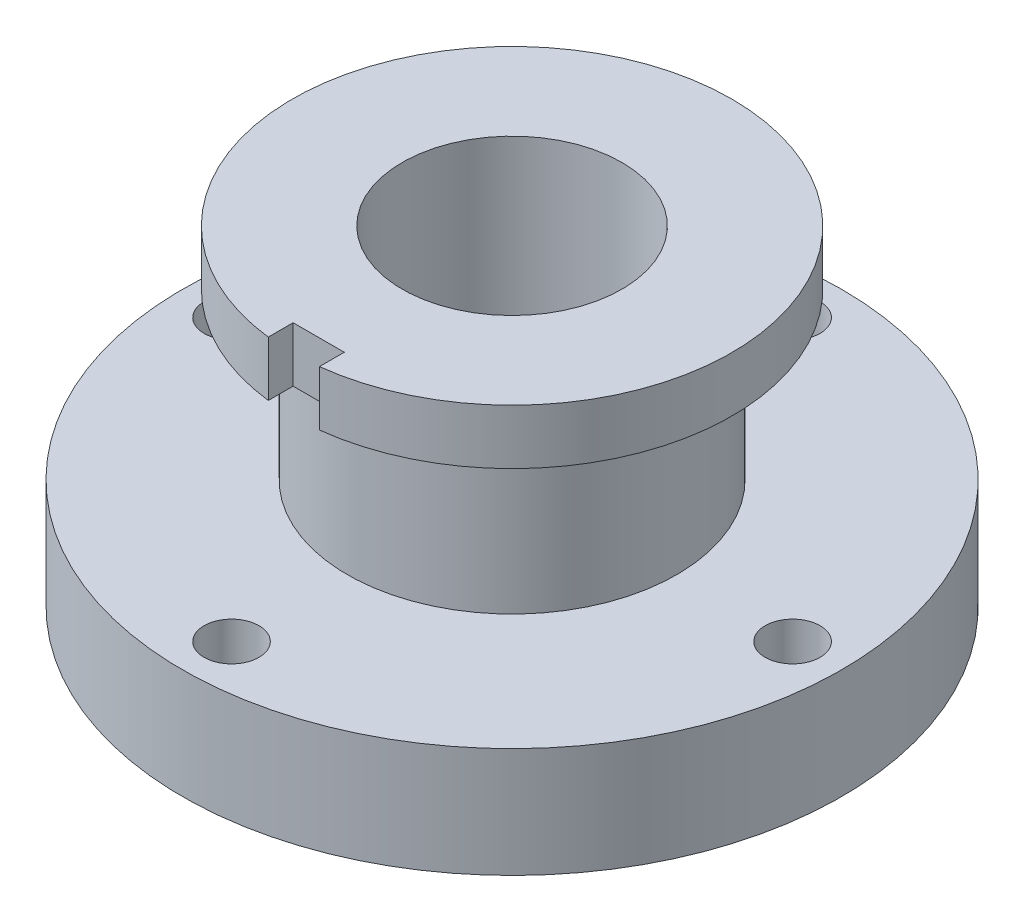
SolidWorks part; units mm, degrees
ref_plane "Front Plane" through (0, 0, 0) normal (0, 0, 1) x (1, 0, 0)
ref_plane "Top Plane" through (0, 0, 0) normal (0, 1, 0) x (1, 0, 0)
ref_plane "Right Plane" through (0, 0, 0) normal (1, 0, 0) x (0, 0, -1)
other "Center of Mass"
sketch "Sketch4" plane through (0, 0, 0) normal (0, 0, 1) x (1, 0, 0)
  line L0 (0, -251.6129) -> (0, -151.6129)
  line L1 (0, -251.6129) -> (300, -251.6129)
  line L2 (300, -251.6129) -> (300, -151.6129)
  line L3 (300, -151.6129) -> (150, -151.6129)
  line L4 (150, -151.6129) -> (150, -1.6129)
  line L5 (150, -1.6129) -> (200, -1.6129)
  line L6 (200, -1.6129) -> (200, 48.3871)
  line L7 (200, 48.3871) -> (152.8226, 48.3871)
  line L8 (152.8226, 48.3871) -> (100, 48.3871)
  line L9 (100, 48.3871) -> (100, -151.6129)
  line L10 (100, -151.6129) -> (0, -151.6129)
  line L11 (0, -251.6129) -> (0, 382.6571) construction
  dimension "D1" = 300
  dimension "D2" = 100
  dimension "D4" = 50
  dimension "D5" = 150
  dimension "D6" = 100
  dimension "D7" = 50
  dimension "D8" = 100
revolve "Revolve2" add sketch "Sketch4" angle 360 about L11
sketch "Sketch5" plane through (0, -151.6129, 0) normal (0, 1, 0) x (1, 0, 0)
  circle A0 centre (0, 255.3655) radius 25
  circle A2 centre (255.3655, 0) radius 25
  circle A3 centre (0, -255.3655) radius 25
  circle A4 centre (-255.3655, 0) radius 25
  dimension "D1" = 4
  dimension "D2" = 50
extrude "Cut-Extrude2" cut sketch "Sketch5" against normal blind 100
ref_axis "Base_Axis" through (0, -266.6129, 0) along (0, 1, 0)
sketch "Sketch6" plane through (0, 48.3871, 0) normal (0, 1, 0) x (1, 0, 0)
  line L1 (-23.2765, -176.0181) -> (23.2765, -176.0181)
  line L2 (-23.2765, -176.0181) -> (-23.2765, -223.9819)
  line L3 (-23.2765, -223.9819) -> (23.2765, -223.9819)
  line L4 (23.2765, -176.0181) -> (23.2765, -223.9819)
  line L5 (-23.2765, -176.0181) -> (23.2765, -223.9819) construction
  line L6 (-23.2765, -223.9819) -> (23.2765, -176.0181) construction
  circle A0 centre (0, 0) radius 200 construction
  point P0 (0, -200)
extrude "Cut-Extrude3" cut sketch "Sketch6" against normal blind 60
